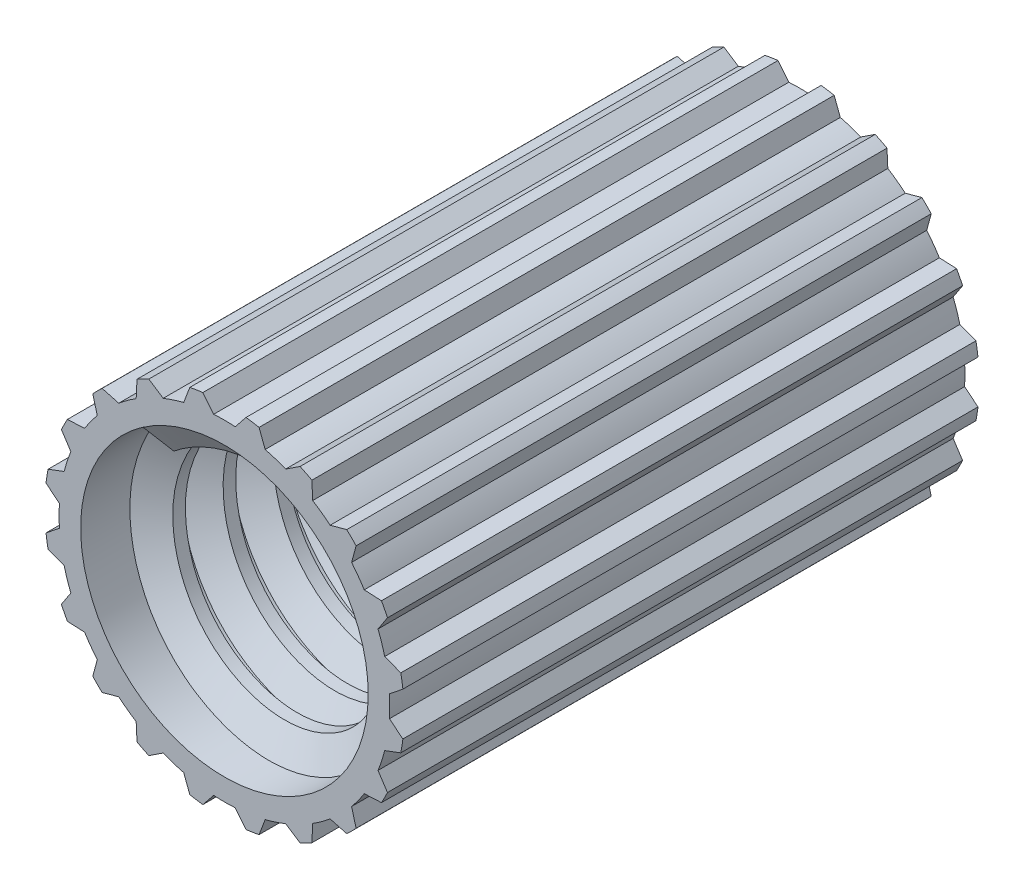
SolidWorks part; units mm, degrees
note: '?' marks a value the reader was unsure of.
material "Brass"
ref_plane "Front Plane" through (0, 0, 0) normal (0, 0, 1) x (1, 0, 0)
ref_plane "Top Plane" through (0, 0, 0) normal (0, 1, 0) x (1, 0, 0)
ref_plane "Right Plane" through (0, 0, 0) normal (1, 0, 0) x (0, 0, -1)
ref_axis "CentralAxis" through (0, 0, 51.25) along (0, 0, -1)?
sketch "BodyS" plane through (0, 0, 0) normal (0, 0, -1) x (-1, 0, 0)
  circle A0 centre (0, 0) radius 2.5
  dimension "C" = 5
extrude "Body" add sketch "BodyS" along normal mid plane 8
sketch "EngagementCutS" plane through (0, 0, 0) normal (0, 0, -1) x (-1, 0, 0)
  line L0 (0, 2.3) -> (0, 2.5) construction
  line L1 (0.3, 2.4819) -> (0.15, 2.2951)
  line L2 (-0.3, 2.4819) -> (-0.15, 2.2951)
  circle A0 centre (0, 0) radius 2.5 construction
  arc A1 (0.3, 2.4819) -> (-0.3, 2.4819) centre (0, 0) ccw
  circle A2 centre (0, 0) radius 2.3
  arc A3 (0.15, 2.2951) -> (-0.15, 2.2951) centre (0, 0) ccw
  dimension "MinorDiameterWidthCut" = 0.3
  dimension "MajorDiameterWidthCut" = 0.6
  dimension "D1" = 0.2
extrude "EngagementCut" cut sketch "EngagementCutS" against normal through all both and the other way through all
sketch "MajorDiameterCutS" plane through (0, 0, 4) normal (0, 0, 1) x (1, 0, 0)
  circle A0 centre (0, 0) radius 2
  dimension "Thread Od" = 4
pattern_circular "ECCP" count 20 over 360 about axis through (0, 0, 0) along (0, 0, 1) of "EngagementCut"
extrude "MajorDiameterCut" cut sketch "MajorDiameterCutS" against normal through all
thread "Thread1" pitch 0.7 start angle 0, offset 0.05, length 0, pitch 0.7, diameter 4
ref_plane "Plane1" through (2, 0, -3.95) normal (0, -1, 0) x (1, 0, 0)
sketch "Thread Profile1" plane through (2, 0, -3.95) normal (0, -1, 0) x (1, 0, 0)
  line L0 (0, 0) -> (0, 0.7) construction
  line L11 (0, 0) -> (0, 0.6125)
  line L12 (0, 0.6125) -> (-0.3789, 0.3937)
  line L13 (-0.3789, 0.3937) -> (-0.3789, 0.2187)
  line L15 (-0.3789, 0.2187) -> (0, 0)
  line L17 (-0.3789, 0.3062) -> (0, 0.3062) construction
  point P2 (0, 0)
  dimension "Pitch" = 0.7
  dimension "Profile_Angle" = 60
  dimension "Profile_Land" = 0.175
  dimension "Profile_Height" = 0.3789
